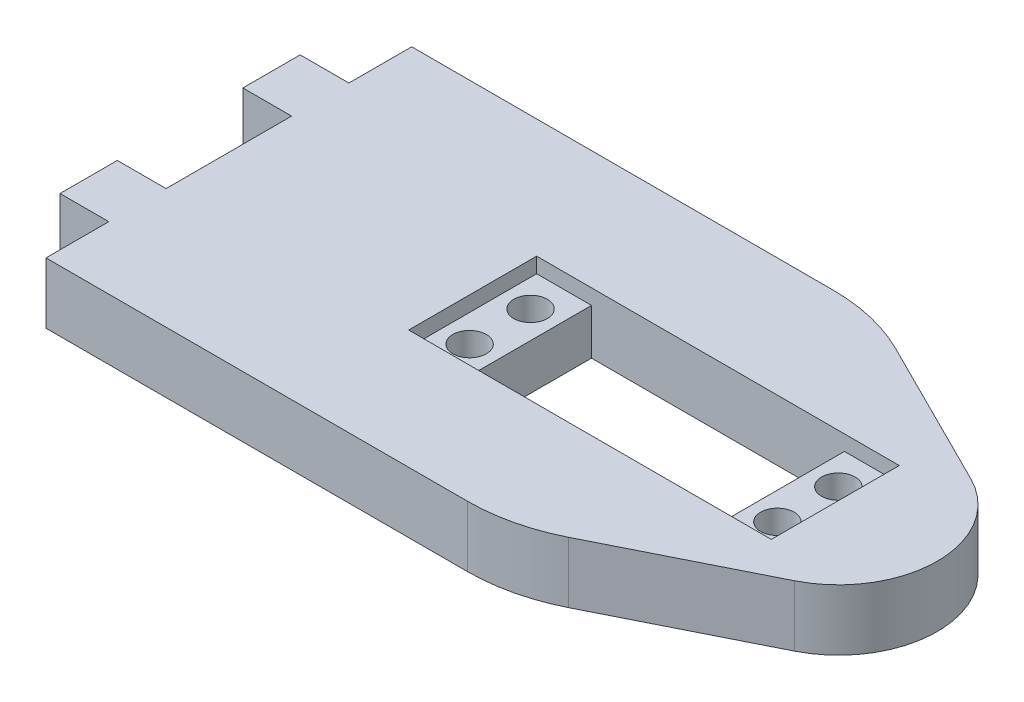
SolidWorks part; units mm, degrees
ref_plane "Front Plane" through (0, 0, 0) normal (0, 0, 1) x (1, 0, 0)
ref_plane "Top Plane" through (0, 0, 0) normal (0, 1, 0) x (1, 0, 0)
ref_plane "Right Plane" through (0, 0, 0) normal (1, 0, 0) x (0, 0, -1)
sketch "Sketch1" plane through (0, 0, 0) normal (0, 1, 0) x (1, 0, 0)
  line L0 (0, 0) -> (0, 10)
  line L13 (0, 10) -> (-8, 10)
  line L14 (-8, 10) -> (-8, 20)
  line L16 (-8, 20) -> (0, 20)
  line L17 (0, 20) -> (0, 40)
  line L18 (0, 40) -> (-8, 40)
  line L19 (-8, 40) -> (-8, 50)
  line L20 (-8, 50) -> (0, 50)
  line L21 (0, 50) -> (0, 60)
  line L22 (0, 60) -> (50, 60)
  line L23 (50, 60) -> (90, 40)
  line L24 (90, 40) -> (90, 20)
  line L25 (90, 20) -> (50, 0)
  line L26 (50, 0) -> (0, 0)
  dimension "D1" = 10
  dimension "D2" = 10
  dimension "D3" = 20
  dimension "D4" = 10
  dimension "D5" = 10
  dimension "D6" = 8
  dimension "D7" = 8
  dimension "D8" = 50
  dimension "D9" = 40
  dimension "D10" = 50
  dimension "D11" = 20
  dimension "D12" = 20
extrude "Boss-Extrude2" add sketch "Sketch1" along normal blind 10
sketch "Sketch5" plane through (0, 10, 0) normal (0, 1, 0) x (1, 0, 0)
  line L0 (90, 40) -> (50, 60) construction
  line L1 (50, 0) -> (90, 20) construction
  line L2 (90, 20) -> (90, 40) construction
  line L3 (81.0557, 44.4721) -> (90, 40)
  line L4 (90, 40) -> (90, 20)
  line L5 (90, 20) -> (81.0557, 15.5279)
  arc A0 (81.0557, 44.4721) -> (81.0557, 15.5279) centre (73.8197, 30) cw
  line M2 (50, 0) -> (90, 20)
  line M3 (90, 20) -> (90, 40)
  line M4 (90, 40) -> (50, 60)
extrude "Cut-Extrude2" cut sketch "Sketch5" against normal blind 10 contours A0 L4 M4 | A0 M3 M2 region at (88.1125, 10, -21.1665) region at (88.1125, 10, -38.8335)
fillet "Fillet3" radius 16 2 edges at (50, 5, -60) (50, 5, 0)
sketch "Sketch8" plane through (0, 10, 0) normal (0, 1, 0) x (1, 0, 0)
  line L0 (-8, 50) -> (-8, 40) construction
  line L1 (0, 50) -> (-8, 50)
  line L2 (0, 50) -> (0, 49.7)
  line L3 (0, 49.7) -> (-8, 49.7)
  line L4 (-8, 50) -> (-8, 49.7)
  line L6 (0, 40) -> (-8, 40)
  line L7 (0, 40) -> (0, 40.3)
  line L8 (0, 40.3) -> (-8, 40.3)
  line L9 (-8, 40) -> (-8, 40.3)
  line L11 (-8, 20) -> (-8, 19.7)
  line L12 (0, 19.7) -> (-8, 19.7)
  line L13 (0, 20) -> (0, 19.7)
  line L14 (0, 20) -> (-8, 20)
  line L15 (-8, 10) -> (-8, 10.3)
  line L16 (0, 10.3) -> (-8, 10.3)
  line L17 (0, 10) -> (0, 10.3)
  line L18 (0, 10) -> (-8, 10)
  dimension "D1" = 0.3
  dimension "D2" = 0.3
extrude "Cut-Extrude5" cut sketch "Sketch8" against normal blind 10
sketch "Sketch9" plane through (0, 10, 0) normal (0, 1, 0) x (1, 0, 0)
  line L0 (0, 40.3) -> (0, 19.7) construction
  line L1 (99.5, 40.5) -> (40, 40.5)
  line L2 (99.5, 40.5) -> (99.5, 19.5)
  line L3 (99.5, 19.5) -> (40, 19.5)
  line L4 (40, 40.5) -> (40, 19.5)
  arc A0 (81.0557, 15.5279) -> (81.0557, 44.4721) centre (73.8197, 30) ccw construction
  point P4 (80, 30)
  point P8 (90, 30)
  dimension "D1" = 21
  dimension "D2" = 59.5
  dimension "D3" = 19.5
  dimension "D4" = 10.5
  dimension "D5" = 80
sketch "Sketch11" plane through (0, 0, 0) normal (0, -1, 0) x (1, 0, 0)
  line L0 (46.2229, 0) -> (76.2229, 0)
  line L1 (76.2229, 0) -> (107.2786, -15.5279)
  line L2 (46.2229, 0) -> (46.2229, -60)
  line L3 (46.2229, -60) -> (76.2229, -60)
  line L4 (76.2229, -60) -> (107.2786, -44.4721)
  line L5 (53.3783, -1.6892) -> (81.0557, -15.5279) construction
  line L6 (81.0557, -44.4721) -> (53.3783, -58.3108) construction
  arc A0 (107.2786, -44.4721) -> (107.2786, -15.5279) centre (100.0426, -30) ccw
  arc A1 (81.0557, -44.4721) -> (81.0557, -15.5279) centre (73.8197, -30) ccw construction
  dimension "D1" = 30
extrude "Boss-Extrude3" add sketch "Sketch11" against normal blind 10
extrude "Cut-Extrude7" cut sketch "Sketch9" against normal blind 2.5
sketch "Sketch12" plane through (0, 7.5, 0) normal (0, 1, 0) x (1, 0, 0)
  line L0 (40, 19.5) -> (99.5, 19.5) construction
  line L4 (90.5, 40.5) -> (90.5, 19.5)
  line L5 (69.75, 20.0806) -> (69.75, 19.5) construction
  line L7 (49, 40.5) -> (49, 19.5)
  line L11 (49, 19.5) -> (90.5, 19.5)
  line L12 (90.5, 40.5) -> (49, 40.5)
  line L13 (90.5, 40.5) -> (90.5, 20.0806)
  line L15 (49, 40.5) -> (49, 20.0806)
  circle A0 centre (95, 35) radius 2.75
  circle A1 centre (95, 25) radius 2.75
  circle A2 centre (44.5, 25) radius 2.75
  circle A3 centre (44.5, 35) radius 2.75
  line M6 (99.5, 40.5) -> (40, 40.5)
  line M8 (40, 19.5) -> (99.5, 19.5)
  dimension "D2" = 5.5
  dimension "D3" = 5.5
extrude "Cut-Extrude9" cut sketch "Sketch12" against normal through all both and the other way through all contours A0 | A1 | L7 L11 L4 M6 M8 | A3 | A2 region at (69.75, 7.5, -30) region at (95, 7.5, -35) region at (95, 7.5, -25) region at (44.5, 7.5, -25) region at (44.5, 7.5, -35)
fillet "Fillet4" radius 30 2 edges at (76.2229, 5, -60) (76.2229, 5, 0)
